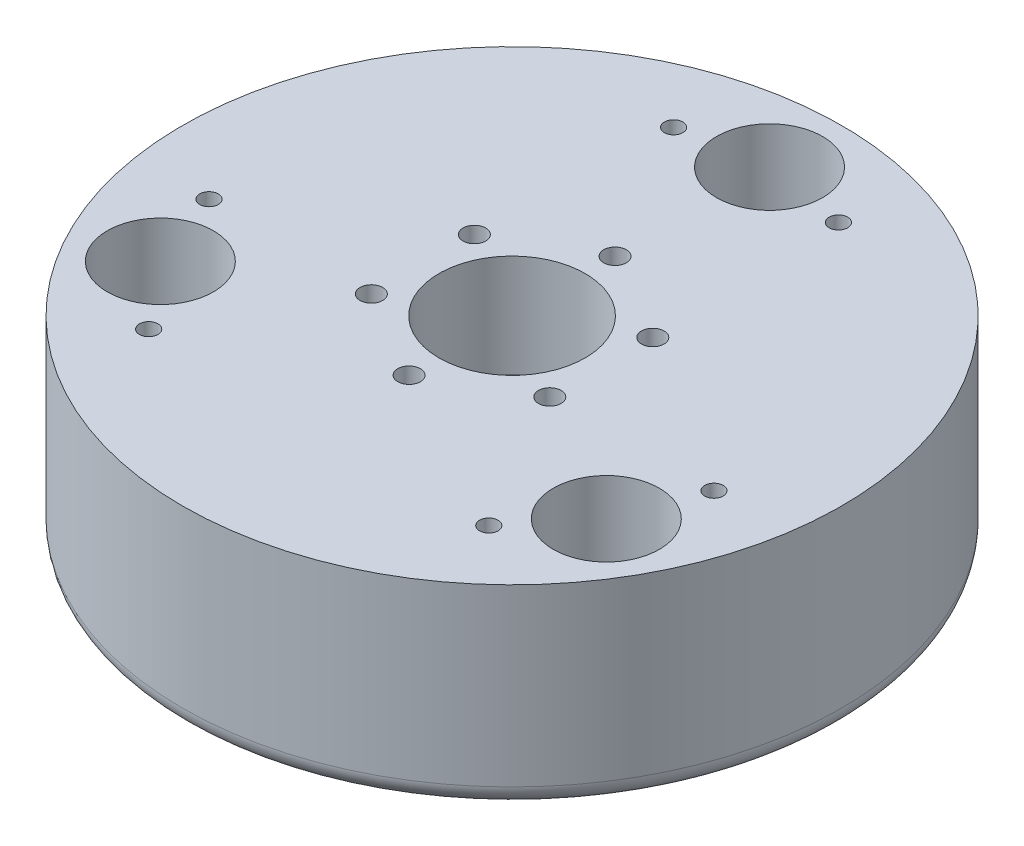
SolidWorks part; units mm, degrees
ref_plane "Спереди" through (0, 0, 0) normal (0, 0, 1) x (1, 0, 0)
ref_plane "Сверху" through (0, 0, 0) normal (0, 1, 0) x (1, 0, 0)
ref_plane "Справа" through (0, 0, 0) normal (1, 0, 0) x (0, 0, -1)
sketch "Эскиз1" plane through (0, 0, 0) normal (0, 1, 0) x (1, 0, 0)
  circle A3 centre (0, 0) radius 32
  circle A4 centre (0, 0) radius 4
  circle A6 centre (0, 0) radius 25 construction
  circle A7 centre (0, 25) radius 3
  circle A8 centre (21.6506, -12.5) radius 3
  circle A9 centre (-21.6506, -12.5) radius 3
  dimension "D4" = 64
  dimension "D1" = 8
  dimension "D2" = 50
  dimension "D3" = 6
  dimension "D5" = 3
extrude "Бобышка-Вытянуть1" add sketch "Эскиз1" along normal blind 19
fillet "Скругление1" radius 2 1 edges at (0, 0, 32)
sketch "Эскиз2" plane through (0, 19, 0) normal (0, 1, 0) x (1, 0, 0)
  circle A0 centre (0, 25) radius 5.15
  circle A2 centre (21.6506, -12.5) radius 5.15
  circle A3 centre (-21.6506, -12.5) radius 5.15
  circle A4 centre (-21.6506, -12.5) radius 3 construction
  dimension "D1" = 10.3
  dimension "D2" = 3
extrude "Вырез-Вытянуть1" cut sketch "Эскиз2" against normal blind 15.2
sketch "Эскиз3" plane through (0, 0, 0) normal (0, -1, 0) x (1, 0, 0)
  circle A0 centre (0, 0) radius 25 construction
  circle A1 centre (0, 25) radius 2.55
  circle A2 centre (21.6506, -12.5) radius 2.55
  circle A3 centre (-21.6506, -12.5) radius 2.55
  dimension "D2" = 3
  dimension "D1" = 5.1
extrude "Вырез-Вытянуть2" cut sketch "Эскиз3" against normal blind 15
sketch "Эскиз4" plane through (0, 19, 0) normal (0, 1, 0) x (1, 0, 0)
  circle A0 centre (0, 0) radius 10 construction
  circle A1 centre (0, 10) radius 1.1
  circle A2 centre (8.6603, 5) radius 1.1
  circle A3 centre (8.6603, -5) radius 1.1
  circle A4 centre (0, -10) radius 1.1
  circle A5 centre (-8.6603, -5) radius 1.1
  circle A6 centre (-8.6603, 5) radius 1.1
  dimension "D3" = 6
  dimension "D1" = 20
  dimension "D2" = 2.2
extrude "Вырез-Вытянуть3" cut sketch "Эскиз4" against normal through all
sketch "Эскиз7" plane through (0, 0, 0) normal (0, -1, 0) x (1, 0, 0)
  circle A0 centre (0, 10) radius 1.8 construction
  circle A7 centre (8.6603, 5) radius 1.8
  circle A8 centre (8.6603, -5) radius 1.8 construction
  circle A9 centre (0, -10) radius 1.8
  circle A10 centre (-8.6603, -5) radius 1.8 construction
  circle A11 centre (-8.6603, 5) radius 1.8
  circle A12 centre (8.6603, 5) radius 1.1 construction
  dimension "D1" = 3.6
  dimension "D2" = 6
extrude "Вырез-Вытянуть5" cut sketch "Эскиз7" against normal offset from surface (3 mm away) 16 up to face at (0, 19, -8.9)
chamfer "Фаска1" distance 1 angle 45 7 edges at (21.6506, 0, -15.05) (0, 0, -22) (-21.6506, 0, -15.05) (-21.6506, 0, 15.5) (0, 0, 22.45) (21.6506, 0, 15.5) (0, 0, 4)
sketch "Эскиз8" plane through (0, 19, 0) normal (0, 1, 0) x (1, 0, 0)
  circle A0 centre (0, 0) radius 7.1
  dimension "D1" = 14.2
extrude "Вырез-Вытянуть6" cut sketch "Эскиз8" against normal blind 10
sketch "Эскиз9" plane through (0, 19, 0) normal (0, 1, 0) x (1, 0, 0)
  line L0 (0, 0) -> (0, 25) construction
  line L1 (-8, 23.6854) -> (8, 23.6854) construction
  circle A0 centre (0, 0) radius 25 construction
  circle A1 centre (-8, 23.6854) radius 0.9
  circle A2 centre (8, 23.6854) radius 0.9
  circle A3 centre (16.5122, -18.7709) radius 0.9
  circle A4 centre (24.5122, -4.9145) radius 0.9
  circle A5 centre (-24.5122, -4.9145) radius 0.9
  circle A6 centre (-16.5122, -18.7709) radius 0.9
  dimension "D1" = 16
  dimension "D2" = 1.8
  dimension "D3" = 1.8
extrude "Вырез-Вытянуть7" cut sketch "Эскиз9" against normal through all
equation "\"motor_diameter\"= 30"
equation "\"mm_diameter\"= IIF ( \"motor_diameter\" < 34 , 41 , \"motor_diameter\" + 8 )"
equation "\"upper_shafts_diameter\"= 5"
equation "\"upper_shats_length\"= 180"
equation "\"upper_bearing_d1\"= 10"
equation "\"upper_bearing_d2\"= 5"
equation "\"upper_bearing_h\"= 15"
equation "\"lower_shafts_diameter\"= 5"
equation "\"lower_shafts_length\"= 180"
equation "\"lower_bearing_d1\"= 10"
equation "\"lower_bearing_d2\"= 5"
equation "\"lower_bearing_h\"= 15"
equation "\"print_offset\"= 0.2"
equation "\"bh_screws_d\"= 2"
equation "\"bh_screws_h\"= 20"
equation "\"bh_screws_hh_d\"= 3.4"
equation "\"bh_screws_hh_h\"= 2"
equation "\"bh_nut_d\"= 3.8"
equation "\"bh_nut_h\"= 2"
equation "\"motor_screws_d\"= 3"
equation "\"motor_screws_h\"= 16"
equation "\"motor_screws_hh_d\"= 5.5"
equation "\"motor_screws_hh_h\"= 3"
equation "\"plate_hole_distance\"= 25.4"
equation "\"plate_screws_d\"= 6.5"
equation "\"shafts_diameter\"= IIF ( \"mm_diameter\" < 42 , 42 + 8 , \"mm_diameter\" + 8 )"
equation "\"D4@Эскиз1\"= \"system_radius\" * 2"
equation "\"central_hole_diameter\"= 8"
equation "\"bh_thikness\"= 4"
equation "\"D1@Эскиз1\"=\"central_hole_diameter\""
equation "\"D2@Эскиз1\"=\"shafts_diameter\""
equation "\"D3@Эскиз1\" = \"lower_shafts_diameter\" + 1"
equation "\"D1@Бобышка-Вытянуть1\" = \"bh_thikness\" + \"lower_bearing_h\""
equation "\"D1@Эскиз2\" = \"lower_bearing_d1\" + \"print_offset\" * 1.5"
equation "\"D1@Вырез-Вытянуть1\" = \"lower_bearing_h\" + \"print_offset\""
equation "\"D1@Эскиз3\" = \"upper_shafts_diameter\" + \"print_offset\" / 2"
equation "\"D1@Вырез-Вытянуть2\"= \"upper_bearing_h\""
equation "\"D2@Эскиз4\"=\"bh_screws_d\"+\"print_offset\""
equation "\"D1@Вырез-Вытянуть5\"=\"bh_screws_h\"-\"bh_thikness\""
equation "\"D1@Эскиз7\"=\"bh_screws_hh_d\"+\"print_offset\""
equation "\"D1@Вырез-Вытянуть6\"=14-\"bh_thikness\""
equation "\"D2@Эскиз9\"=\"bh_screws_d\"-\"print_offset\""
equation "\"D3@Эскиз9\"=\"D2@Эскиз9\""
equation "\"ends_screws_d\"= 4"
equation "\"ends_screws_h\"= 16"
equation "\"ends_screws_hh_d\"= 6.7"
equation "\"ends_screws_hh_h\"= 4.1"
equation "\"ends_nut_d\"= 6.8"
equation "\"ends_nut_h\"= 3"
equation "\"system_radius\" = ( \"shafts_diameter\" + 12 + \"bh_thikness\" / 2 ) / 2"
equation "\"encoder_distance\"= \"system_radius\" + 4"
equation "\"tape_position\"= \"encoder_distance\" - 2 + 3.9 + 1.7 / 2"
equation "\"ft_sensor_d1\" = 9.8"
equation "\"ft_sensor_d2\"= 24.9"
equation "\"ft_sensor_h\"= 7"
equation "\"carbon_pipe_d\"= 14"
equation "\"D1@Эскиз8\"=\"print_offset\"+14.00мм"
